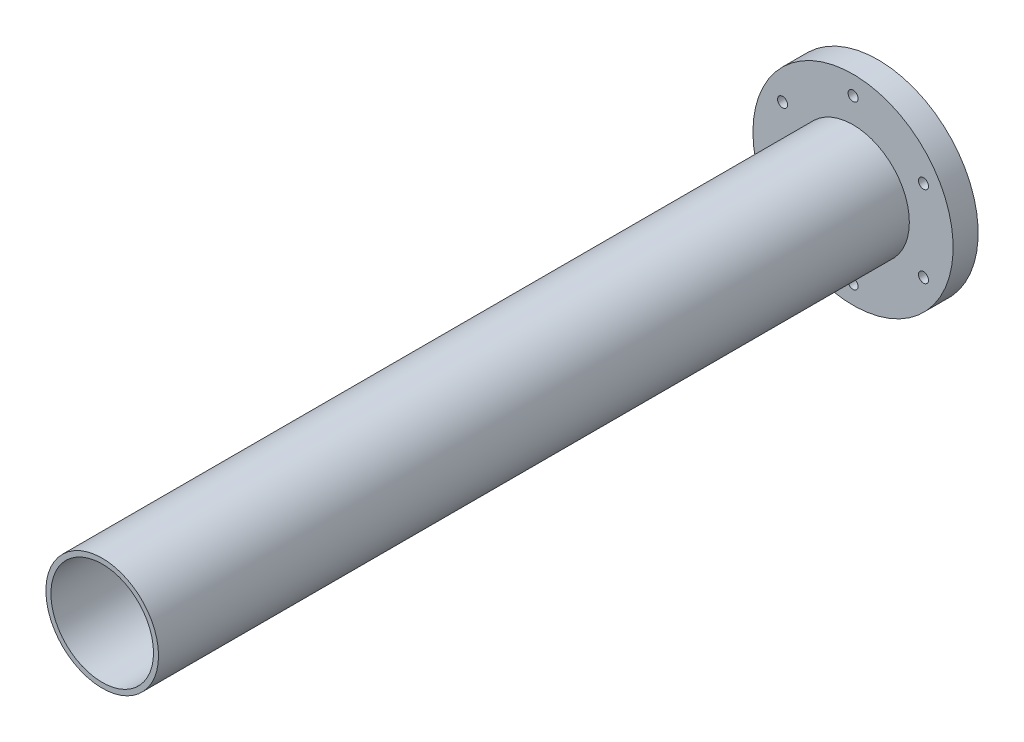
SolidWorks part; units mm, degrees
ref_plane "Front Plane" through (0, 0, 0) normal (0, 0, 1) x (1, 0, 0)
ref_plane "Top Plane" through (0, 0, 0) normal (0, 1, 0) x (1, 0, 0)
ref_plane "Right Plane" through (0, 0, 0) normal (1, 0, 0) x (0, 0, -1)
sketch "Sketch1" plane through (0, 0, 0) normal (0, 0, 1) x (1, 0, 0)
  circle A0 centre (0, 0) radius 22.5
  circle A1 centre (0, 0) radius 20.5
  dimension "D1" = 45
  dimension "D2" = 41
extrude "Boss-Extrude1" add sketch "Sketch1" along normal blind 300
sketch "Sketch2" plane through (0, 0, 0) normal (0, 0, -1) x (-1, 0, 0)
  circle A0 centre (0, 0) radius 40
  circle A1 centre (0, 0) radius 32.5 construction
  circle A2 centre (0, 32.5) radius 2
  circle A3 centre (28.1458, 16.25) radius 2
  circle A4 centre (28.1458, -16.25) radius 2
  circle A5 centre (0, -32.5) radius 2
  circle A6 centre (-28.1458, -16.25) radius 2
  circle A7 centre (-28.1458, 16.25) radius 2
  point P18 (0, 0)
  dimension "D1" = 80
  dimension "D2" = 65
  dimension "D3" = 6
  dimension "D4" = 4
extrude "Boss-Extrude2" add sketch "Sketch2" along normal blind 10
